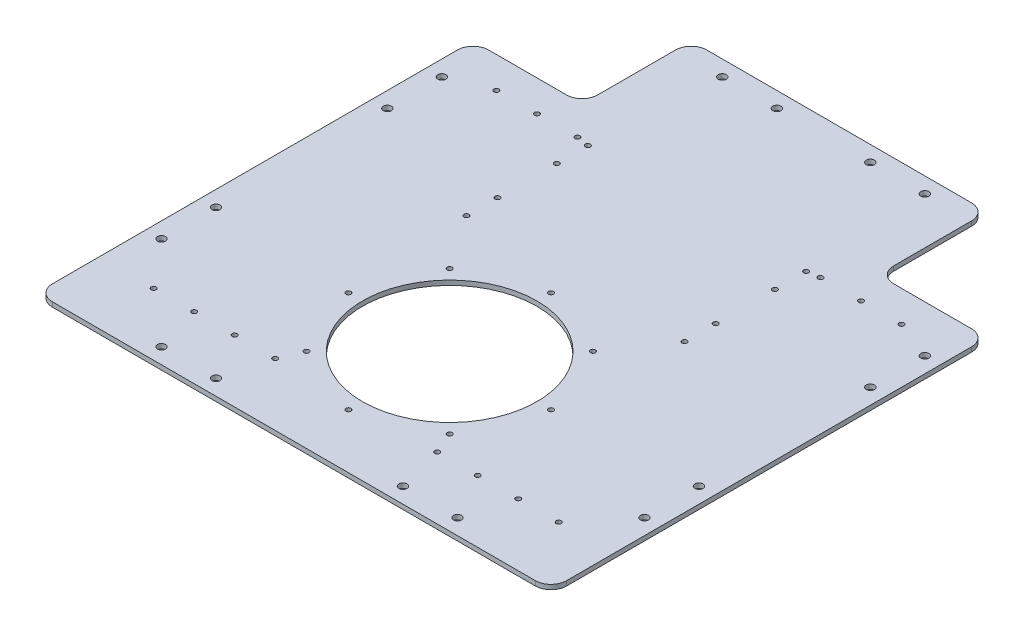
SolidWorks part; units mm, degrees
ref_plane "Front Plane" through (0, 0, 0) normal (0, 0, 1) x (1, 0, 0)
ref_plane "Top Plane" through (0, 0, 0) normal (0, 1, 0) x (1, 0, 0)
ref_plane "Right Plane" through (0, 0, 0) normal (1, 0, 0) x (0, 0, -1)
sketch "Sketch1" plane through (0, 0, 0) normal (0, 1, 0) x (1, 0, 0)
  line L1 (0, 0) -> (330, 0) construction
  line L2 (0, 0) -> (0, 350) construction
  line L3 (0, 350) -> (330, 350) construction
  line L4 (330, 0) -> (330, 350) construction
  line L5 (0, 0) -> (330, 0)
  line L6 (0, 0) -> (0, 280)
  line L7 (0, 280) -> (330, 280)
  line L8 (330, 0) -> (330, 280)
  line L9 (70, 280) -> (260, 280)
  line L10 (70, 280) -> (70, 350)
  line L11 (70, 350) -> (260, 350)
  line L12 (260, 280) -> (260, 350)
  circle A0 centre (165, 100) radius 56
  point P11 (165, 350)
  point P12 (165, 350)
  dimension "D5" = 112
  dimension "D1" = 330
  dimension "D2" = 350
  dimension "D3" = 70
  dimension "D4" = 70
  dimension "D6" = 100
extrude "Boss-Extrude1" add sketch "Sketch1" along normal blind 3 contours L5 L8 L7 L6 A0 | L7 L12 L11 L10 region at (4.3278, 0, -140) region at (165, 0, -315)
fillet "Fillet1" radius 10 8 edges at (0, 1.5, 0) (330, 1.5, 0) (330, 1.5, -280) (260, 1.5, -350) (260, 1.5, -280) (70, 1.5, -280) (70, 1.5, -350) (0, 1.5, -280)
sketch "Sketch2" plane through (0, 3, 0) normal (0, 1, 0) x (1, 0, 0)
  line L0 (80, 350) -> (250, 350) construction
  line L1 (0, 0) -> (330, 0) construction
  line L2 (0, 0) -> (0, 350) construction
  line L3 (0, 350) -> (330, 350) construction
  line L4 (330, 0) -> (330, 350) construction
  line L5 (330, 10) -> (330, 270) construction
  line L6 (20, 20) -> (20, 330) construction
  line L7 (20, 330) -> (310, 330) construction
  line L8 (310, 20) -> (310, 330) construction
  line L9 (20, 20) -> (310, 20) construction
  line L10 (10, 10) -> (10, 340) construction
  line L11 (10, 340) -> (320, 340) construction
  line L12 (320, 10) -> (320, 340) construction
  line L13 (10, 10) -> (320, 10) construction
  line L14 (10, 280) -> (60, 280) construction
  line L15 (270, 280) -> (320, 280) construction
  line L16 (70, 290) -> (70, 340) construction
  line L17 (260, 290) -> (260, 340) construction
  line L19 (35, 40) -> (295, 40) construction
  line L20 (35, 40) -> (35, 260) construction
  line L21 (35, 260) -> (295, 260) construction
  line L22 (295, 40) -> (295, 260) construction
  circle A0 centre (100, 340) radius 2.6
  circle A1 centre (230, 340) radius 2.6
  circle A2 centre (320, 250) radius 2.6
  circle A3 centre (320, 70) radius 2.6
  circle A4 centre (260, 10) radius 2.6
  circle A5 centre (10, 70) radius 2.6
  circle A6 centre (70, 10) radius 2.6
  circle A7 centre (10, 250) radius 2.6
  circle A8 centre (165, 100) radius 65 construction
  circle A10 centre (165, 165) radius 1.6
  circle A18 centre (35, 260) radius 1.6
  circle A19 centre (61, 260) radius 1.6
  circle A20 centre (87, 260) radius 1.6
  circle A26 centre (243, 260) radius 1.6
  circle A27 centre (269, 260) radius 1.6
  circle A28 centre (295, 260) radius 1.6
  circle A29 centre (35, 40) radius 1.6
  circle A30 centre (61, 40) radius 1.6
  circle A31 centre (87, 40) radius 1.6
  circle A32 centre (113, 40) radius 1.6
  circle A40 centre (10, 215) radius 2.6
  circle A41 centre (10, 105) radius 2.6
  circle A42 centre (105, 10) radius 2.6
  circle A43 centre (225, 10) radius 2.6
  circle A44 centre (320, 105) radius 2.6
  circle A45 centre (320, 215) radius 2.6
  circle A46 centre (135, 340) radius 2.6
  circle A47 centre (195, 340) radius 2.6
  circle A48 centre (295, 40) radius 1.6
  circle A49 centre (269, 40) radius 1.6
  circle A50 centre (243, 40) radius 1.6
  circle A51 centre (217, 40) radius 1.6
  circle A52 centre (165, 260) radius 1.6 [skipped]
  circle A53 centre (139, 260) radius 1.6 [skipped]
  circle A54 centre (191, 260) radius 1.6 [skipped]
  circle A71 centre (210.9619, 145.9619) radius 1.6
  circle A72 centre (113, 260) radius 1.6 [skipped]
  circle A73 centre (217, 260) radius 1.6 [skipped]
  circle A74 centre (230, 100) radius 1.6
  circle A75 centre (210.9619, 54.0381) radius 1.6
  circle A76 centre (165, 35) radius 1.6
  circle A77 centre (119.0381, 54.0381) radius 1.6
  circle A78 centre (100, 100) radius 1.6
  circle A79 centre (119.0381, 145.9619) radius 1.6
  point P44 (165, 220)
  point P45 (165, 220)
  point P51 (210.9619, 265.9619)
  point P65 (165, 100)
  point P74 (165, 100)
  dimension "D4" = 5.2
  dimension "D5" = 70
  dimension "D8" = 70
  dimension "D9" = 30
  dimension "D11" = 30
  dimension "D12" = 130
  dimension "D13" = 3.2
  dimension "D19" = 3.2
  dimension "D21" = 3.2
  dimension "D3" = 30
  dimension "D6" = 70
  dimension "D7" = 70
  dimension "D10" = 30
  dimension "D15" = 20
  dimension "D16" = 20
  dimension "D17" = 35
  dimension "D18" = 35
  dimension "D23" = 35
  dimension "D24" = 35
  dimension "D25" = 35
  dimension "D26" = 35
  dimension "D27" = 35
  dimension "D28" = 35
  dimension "D29" = 35
  dimension "D30" = 35
  dimension "D31" = 26
  dimension "D33" = 26
  dimension "D1" = 20
  dimension "D2" = 10
  dimension "D20" = 11
  dimension "D22" = 4
  dimension "D32" = 4
  dimension "D14" = 8
extrude "Cut-Extrude1" cut sketch "Sketch2" against normal through all
sketch "Sketch3" plane through (0, 3, 0) normal (0, 1, 0) x (1, 0, 0)
  line L0 (165, 350) -> (165, 0) construction
  line L1 (80, 350) -> (250, 350) construction
  line L2 (10, 0) -> (320, 0) construction
  circle A0 centre (95, 258.75) radius 1.6
  circle A1 centre (95, 238.75) radius 1.6
  circle A2 centre (95, 200.75) radius 1.6
  circle A3 centre (95, 180.75) radius 1.6
  circle A4 centre (235, 180.75) radius 1.6
  circle A5 centre (235, 200.75) radius 1.6
  circle A6 centre (235, 238.75) radius 1.6
  circle A7 centre (235, 258.75) radius 1.6
  dimension "D1" = 3.2
extrude "Cut-Extrude2" cut sketch "Sketch3" against normal through all
